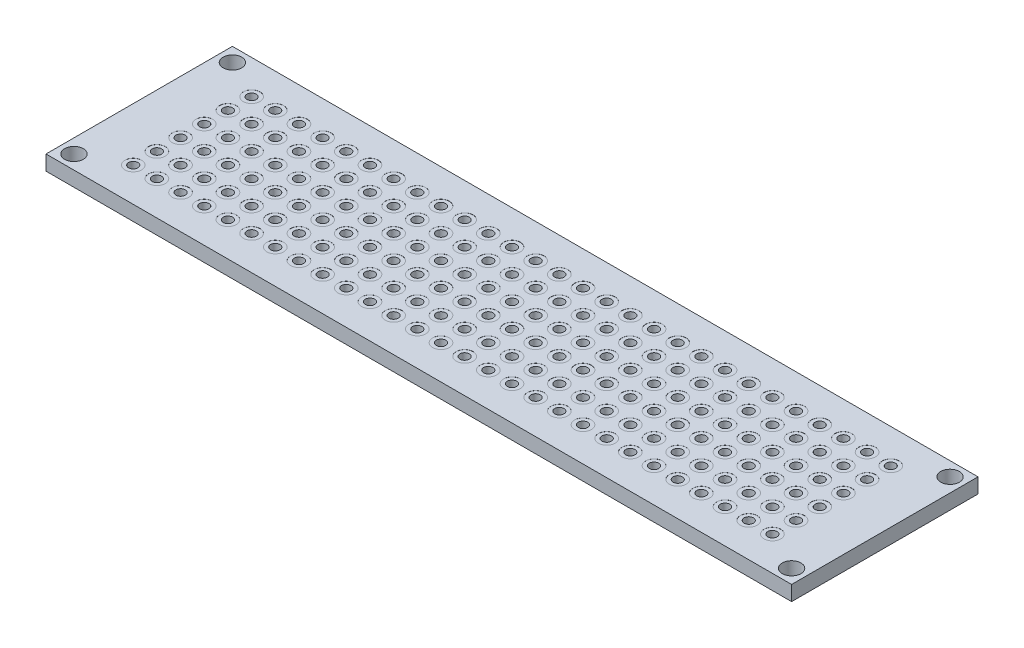
SolidWorks part; units mm, degrees
ref_plane "Front Plane" through (0, 0, 0) normal (0, 0, 1) x (1, 0, 0)
ref_plane "Top Plane" through (0, 0, 0) normal (0, 1, 0) x (1, 0, 0)
ref_plane "Right Plane" through (0, 0, 0) normal (1, 0, 0) x (0, 0, -1)
sketch "Sketch1" plane through (0, 0, 0) normal (0, 1, 0) x (1, 0, 0)
  line L0 (40, 0) -> (40, 20) construction
  line L1 (0, 0) -> (80, 0)
  line L2 (0, 0) -> (0, 20)
  line L3 (0, 20) -> (80, 20)
  line L4 (80, 0) -> (80, 20)
  line L5 (0, 10) -> (80, 10) construction
  circle A0 centre (5.71, 16.35) radius 0.5
  circle A1 centre (5.71, 13.81) radius 0.5
  circle A2 centre (5.71, 11.27) radius 0.5
  circle A3 centre (5.71, 8.73) radius 0.5
  circle A4 centre (5.71, 6.19) radius 0.5
  circle A5 centre (5.71, 3.65) radius 0.5
  circle A6 centre (8.25, 16.35) radius 0.5
  circle A7 centre (8.25, 13.81) radius 0.5
  circle A8 centre (8.25, 11.27) radius 0.5
  circle A9 centre (8.25, 8.73) radius 0.5
  circle A10 centre (8.25, 6.19) radius 0.5
  circle A11 centre (8.25, 3.65) radius 0.5
  circle A12 centre (10.79, 16.35) radius 0.5
  circle A13 centre (10.79, 13.81) radius 0.5
  circle A14 centre (10.79, 11.27) radius 0.5
  circle A15 centre (10.79, 8.73) radius 0.5
  circle A16 centre (10.79, 6.19) radius 0.5
  circle A17 centre (10.79, 3.65) radius 0.5
  circle A18 centre (13.33, 16.35) radius 0.5
  circle A19 centre (13.33, 13.81) radius 0.5
  circle A20 centre (13.33, 11.27) radius 0.5
  circle A21 centre (13.33, 8.73) radius 0.5
  circle A22 centre (13.33, 6.19) radius 0.5
  circle A23 centre (13.33, 3.65) radius 0.5
  circle A24 centre (15.87, 16.35) radius 0.5
  circle A25 centre (15.87, 13.81) radius 0.5
  circle A26 centre (15.87, 11.27) radius 0.5
  circle A27 centre (15.87, 8.73) radius 0.5
  circle A28 centre (15.87, 6.19) radius 0.5
  circle A29 centre (15.87, 3.65) radius 0.5
  circle A30 centre (18.41, 16.35) radius 0.5
  circle A31 centre (18.41, 13.81) radius 0.5
  circle A32 centre (18.41, 11.27) radius 0.5
  circle A33 centre (18.41, 8.73) radius 0.5
  circle A34 centre (18.41, 6.19) radius 0.5
  circle A35 centre (18.41, 3.65) radius 0.5
  circle A36 centre (20.95, 16.35) radius 0.5
  circle A37 centre (20.95, 13.81) radius 0.5
  circle A38 centre (20.95, 11.27) radius 0.5
  circle A39 centre (20.95, 8.73) radius 0.5
  circle A40 centre (20.95, 6.19) radius 0.5
  circle A41 centre (20.95, 3.65) radius 0.5
  circle A42 centre (23.49, 16.35) radius 0.5
  circle A43 centre (23.49, 13.81) radius 0.5
  circle A44 centre (23.49, 11.27) radius 0.5
  circle A45 centre (23.49, 8.73) radius 0.5
  circle A46 centre (23.49, 6.19) radius 0.5
  circle A47 centre (23.49, 3.65) radius 0.5
  circle A48 centre (26.03, 16.35) radius 0.5
  circle A49 centre (26.03, 13.81) radius 0.5
  circle A50 centre (26.03, 11.27) radius 0.5
  circle A51 centre (26.03, 8.73) radius 0.5
  circle A52 centre (26.03, 6.19) radius 0.5
  circle A53 centre (26.03, 3.65) radius 0.5
  circle A54 centre (28.57, 16.35) radius 0.5
  circle A55 centre (28.57, 13.81) radius 0.5
  circle A56 centre (28.57, 11.27) radius 0.5
  circle A57 centre (28.57, 8.73) radius 0.5
  circle A58 centre (28.57, 6.19) radius 0.5
  circle A59 centre (28.57, 3.65) radius 0.5
  circle A60 centre (31.11, 16.35) radius 0.5
  circle A61 centre (31.11, 13.81) radius 0.5
  circle A62 centre (31.11, 11.27) radius 0.5
  circle A63 centre (31.11, 8.73) radius 0.5
  circle A64 centre (31.11, 6.19) radius 0.5
  circle A65 centre (31.11, 3.65) radius 0.5
  circle A66 centre (33.65, 16.35) radius 0.5
  circle A67 centre (33.65, 13.81) radius 0.5
  circle A68 centre (33.65, 11.27) radius 0.5
  circle A69 centre (33.65, 8.73) radius 0.5
  circle A70 centre (33.65, 6.19) radius 0.5
  circle A71 centre (33.65, 3.65) radius 0.5
  circle A72 centre (36.19, 16.35) radius 0.5
  circle A73 centre (36.19, 13.81) radius 0.5
  circle A74 centre (36.19, 11.27) radius 0.5
  circle A75 centre (36.19, 8.73) radius 0.5
  circle A76 centre (36.19, 6.19) radius 0.5
  circle A77 centre (36.19, 3.65) radius 0.5
  circle A78 centre (38.73, 16.35) radius 0.5
  circle A79 centre (38.73, 13.81) radius 0.5
  circle A80 centre (38.73, 11.27) radius 0.5
  circle A81 centre (38.73, 8.73) radius 0.5
  circle A82 centre (38.73, 6.19) radius 0.5
  circle A83 centre (38.73, 3.65) radius 0.5
  circle A84 centre (41.27, 16.35) radius 0.5
  circle A85 centre (41.27, 13.81) radius 0.5
  circle A86 centre (41.27, 11.27) radius 0.5
  circle A87 centre (41.27, 8.73) radius 0.5
  circle A88 centre (41.27, 6.19) radius 0.5
  circle A89 centre (41.27, 3.65) radius 0.5
  circle A90 centre (43.81, 16.35) radius 0.5
  circle A91 centre (43.81, 13.81) radius 0.5
  circle A92 centre (43.81, 11.27) radius 0.5
  circle A93 centre (43.81, 8.73) radius 0.5
  circle A94 centre (43.81, 6.19) radius 0.5
  circle A95 centre (43.81, 3.65) radius 0.5
  circle A96 centre (46.35, 16.35) radius 0.5
  circle A97 centre (46.35, 13.81) radius 0.5
  circle A98 centre (46.35, 11.27) radius 0.5
  circle A99 centre (46.35, 8.73) radius 0.5
  circle A100 centre (46.35, 6.19) radius 0.5
  circle A101 centre (46.35, 3.65) radius 0.5
  circle A102 centre (48.89, 16.35) radius 0.5
  circle A103 centre (48.89, 13.81) radius 0.5
  circle A104 centre (48.89, 11.27) radius 0.5
  circle A105 centre (48.89, 8.73) radius 0.5
  circle A106 centre (48.89, 6.19) radius 0.5
  circle A107 centre (48.89, 3.65) radius 0.5
  circle A108 centre (51.43, 16.35) radius 0.5
  circle A109 centre (51.43, 13.81) radius 0.5
  circle A110 centre (51.43, 11.27) radius 0.5
  circle A111 centre (51.43, 8.73) radius 0.5
  circle A112 centre (51.43, 6.19) radius 0.5
  circle A113 centre (51.43, 3.65) radius 0.5
  circle A114 centre (53.97, 16.35) radius 0.5
  circle A115 centre (53.97, 13.81) radius 0.5
  circle A116 centre (53.97, 11.27) radius 0.5
  circle A117 centre (53.97, 8.73) radius 0.5
  circle A118 centre (53.97, 6.19) radius 0.5
  circle A119 centre (53.97, 3.65) radius 0.5
  circle A120 centre (56.51, 16.35) radius 0.5
  circle A121 centre (56.51, 13.81) radius 0.5
  circle A122 centre (56.51, 11.27) radius 0.5
  circle A123 centre (56.51, 8.73) radius 0.5
  circle A124 centre (56.51, 6.19) radius 0.5
  circle A125 centre (56.51, 3.65) radius 0.5
  circle A126 centre (59.05, 16.35) radius 0.5
  circle A127 centre (59.05, 13.81) radius 0.5
  circle A128 centre (59.05, 11.27) radius 0.5
  circle A129 centre (59.05, 8.73) radius 0.5
  circle A130 centre (59.05, 6.19) radius 0.5
  circle A131 centre (59.05, 3.65) radius 0.5
  circle A132 centre (61.59, 16.35) radius 0.5
  circle A133 centre (61.59, 13.81) radius 0.5
  circle A134 centre (61.59, 11.27) radius 0.5
  circle A135 centre (61.59, 8.73) radius 0.5
  circle A136 centre (61.59, 6.19) radius 0.5
  circle A137 centre (61.59, 3.65) radius 0.5
  circle A138 centre (64.13, 16.35) radius 0.5
  circle A139 centre (64.13, 13.81) radius 0.5
  circle A140 centre (64.13, 11.27) radius 0.5
  circle A141 centre (64.13, 8.73) radius 0.5
  circle A142 centre (64.13, 6.19) radius 0.5
  circle A143 centre (64.13, 3.65) radius 0.5
  circle A144 centre (66.67, 16.35) radius 0.5
  circle A145 centre (66.67, 13.81) radius 0.5
  circle A146 centre (66.67, 11.27) radius 0.5
  circle A147 centre (66.67, 8.73) radius 0.5
  circle A148 centre (66.67, 6.19) radius 0.5
  circle A149 centre (66.67, 3.65) radius 0.5
  circle A150 centre (69.21, 16.35) radius 0.5
  circle A151 centre (69.21, 13.81) radius 0.5
  circle A152 centre (69.21, 11.27) radius 0.5
  circle A153 centre (69.21, 8.73) radius 0.5
  circle A154 centre (69.21, 6.19) radius 0.5
  circle A155 centre (69.21, 3.65) radius 0.5
  circle A156 centre (71.75, 16.35) radius 0.5
  circle A157 centre (71.75, 13.81) radius 0.5
  circle A158 centre (71.75, 11.27) radius 0.5
  circle A159 centre (71.75, 8.73) radius 0.5
  circle A160 centre (71.75, 6.19) radius 0.5
  circle A161 centre (71.75, 3.65) radius 0.5
  circle A162 centre (74.29, 16.35) radius 0.5
  circle A163 centre (74.29, 13.81) radius 0.5
  circle A164 centre (74.29, 11.27) radius 0.5
  circle A165 centre (74.29, 8.73) radius 0.5
  circle A166 centre (74.29, 6.19) radius 0.5
  circle A167 centre (74.29, 3.65) radius 0.5
  circle A168 centre (1.5, 18.5) radius 1
  circle A169 centre (78.5, 18.5) radius 1
  circle A170 centre (1.5, 1.5) radius 1
  circle A171 centre (78.5, 1.5) radius 1
  point P11 (1.3527, 18.7563)
  dimension "D3" = 1
  dimension "D8" = 2
  dimension "D9" = 0.5
  dimension "D10" = 0.5
  dimension "D1" = 80
  dimension "D2" = 20
  dimension "D5" = 2.54
  dimension "D7" = 2.54
  dimension "D4" = 6
  dimension "D6" = 28
extrude "Boss-Extrude1" add sketch "Sketch1" along normal blind 1.6
sketch "Sketch2" plane through (0, 1.6, 0) normal (0, 1, 0) x (1, 0, 0)
  circle A0 centre (5.71, 16.35) radius 0.9
  circle A1 centre (8.25, 16.35) radius 0.9
  circle A2 centre (10.79, 16.35) radius 0.9
  circle A3 centre (13.33, 16.35) radius 0.9
  circle A4 centre (15.87, 16.35) radius 0.9
  circle A5 centre (18.41, 16.35) radius 0.9
  circle A6 centre (20.95, 16.35) radius 0.9
  circle A7 centre (23.49, 16.35) radius 0.9
  circle A8 centre (26.03, 16.35) radius 0.9
  circle A9 centre (28.57, 16.35) radius 0.9
  circle A10 centre (31.11, 16.35) radius 0.9
  circle A11 centre (33.65, 16.35) radius 0.9
  circle A12 centre (36.19, 16.35) radius 0.9
  circle A13 centre (38.73, 16.35) radius 0.9
  circle A14 centre (41.27, 16.35) radius 0.9
  circle A15 centre (43.81, 16.35) radius 0.9
  circle A16 centre (46.35, 16.35) radius 0.9
  circle A17 centre (48.89, 16.35) radius 0.9
  circle A18 centre (51.43, 16.35) radius 0.9
  circle A19 centre (53.97, 16.35) radius 0.9
  circle A20 centre (56.51, 16.35) radius 0.9
  circle A21 centre (59.05, 16.35) radius 0.9
  circle A22 centre (61.59, 16.35) radius 0.9
  circle A23 centre (64.13, 16.35) radius 0.9
  circle A24 centre (66.67, 16.35) radius 0.9
  circle A25 centre (69.21, 16.35) radius 0.9
  circle A26 centre (71.75, 16.35) radius 0.9
  circle A27 centre (74.29, 16.35) radius 0.9
  circle A28 centre (8.25, 13.81) radius 0.9
  circle A29 centre (10.79, 13.81) radius 0.9
  circle A30 centre (13.33, 13.81) radius 0.9
  circle A31 centre (15.87, 13.81) radius 0.9
  circle A32 centre (18.41, 13.81) radius 0.9
  circle A33 centre (20.95, 13.81) radius 0.9
  circle A34 centre (23.49, 13.81) radius 0.9
  circle A35 centre (26.03, 13.81) radius 0.9
  circle A36 centre (28.57, 13.81) radius 0.9
  circle A37 centre (31.11, 13.81) radius 0.9
  circle A38 centre (33.65, 13.81) radius 0.9
  circle A39 centre (36.19, 13.81) radius 0.9
  circle A40 centre (38.73, 13.81) radius 0.9
  circle A41 centre (41.27, 13.81) radius 0.9
  circle A42 centre (43.81, 13.81) radius 0.9
  circle A43 centre (46.35, 13.81) radius 0.9
  circle A44 centre (48.89, 13.81) radius 0.9
  circle A45 centre (51.43, 13.81) radius 0.9
  circle A46 centre (53.97, 13.81) radius 0.9
  circle A47 centre (56.51, 13.81) radius 0.9
  circle A48 centre (59.05, 13.81) radius 0.9
  circle A49 centre (61.59, 13.81) radius 0.9
  circle A50 centre (64.13, 13.81) radius 0.9
  circle A51 centre (66.67, 13.81) radius 0.9
  circle A52 centre (69.21, 13.81) radius 0.9
  circle A53 centre (71.75, 13.81) radius 0.9
  circle A54 centre (74.29, 13.81) radius 0.9
  circle A55 centre (8.25, 11.27) radius 0.9
  circle A56 centre (10.79, 11.27) radius 0.9
  circle A57 centre (13.33, 11.27) radius 0.9
  circle A58 centre (15.87, 11.27) radius 0.9
  circle A59 centre (18.41, 11.27) radius 0.9
  circle A60 centre (20.95, 11.27) radius 0.9
  circle A61 centre (23.49, 11.27) radius 0.9
  circle A62 centre (26.03, 11.27) radius 0.9
  circle A63 centre (28.57, 11.27) radius 0.9
  circle A64 centre (31.11, 11.27) radius 0.9
  circle A65 centre (33.65, 11.27) radius 0.9
  circle A66 centre (36.19, 11.27) radius 0.9
  circle A67 centre (38.73, 11.27) radius 0.9
  circle A68 centre (41.27, 11.27) radius 0.9
  circle A69 centre (43.81, 11.27) radius 0.9
  circle A70 centre (46.35, 11.27) radius 0.9
  circle A71 centre (48.89, 11.27) radius 0.9
  circle A72 centre (51.43, 11.27) radius 0.9
  circle A73 centre (53.97, 11.27) radius 0.9
  circle A74 centre (56.51, 11.27) radius 0.9
  circle A75 centre (59.05, 11.27) radius 0.9
  circle A76 centre (61.59, 11.27) radius 0.9
  circle A77 centre (64.13, 11.27) radius 0.9
  circle A78 centre (66.67, 11.27) radius 0.9
  circle A79 centre (69.21, 11.27) radius 0.9
  circle A80 centre (71.75, 11.27) radius 0.9
  circle A81 centre (74.29, 11.27) radius 0.9
  circle A82 centre (8.25, 8.73) radius 0.9
  circle A83 centre (10.79, 8.73) radius 0.9
  circle A84 centre (13.33, 8.73) radius 0.9
  circle A85 centre (15.87, 8.73) radius 0.9
  circle A86 centre (18.41, 8.73) radius 0.9
  circle A87 centre (20.95, 8.73) radius 0.9
  circle A88 centre (23.49, 8.73) radius 0.9
  circle A89 centre (26.03, 8.73) radius 0.9
  circle A90 centre (28.57, 8.73) radius 0.9
  circle A91 centre (31.11, 8.73) radius 0.9
  circle A92 centre (33.65, 8.73) radius 0.9
  circle A93 centre (36.19, 8.73) radius 0.9
  circle A94 centre (38.73, 8.73) radius 0.9
  circle A95 centre (41.27, 8.73) radius 0.9
  circle A96 centre (43.81, 8.73) radius 0.9
  circle A97 centre (46.35, 8.73) radius 0.9
  circle A98 centre (48.89, 8.73) radius 0.9
  circle A99 centre (51.43, 8.73) radius 0.9
  circle A100 centre (53.97, 8.73) radius 0.9
  circle A101 centre (56.51, 8.73) radius 0.9
  circle A102 centre (59.05, 8.73) radius 0.9
  circle A103 centre (61.59, 8.73) radius 0.9
  circle A104 centre (64.13, 8.73) radius 0.9
  circle A105 centre (66.67, 8.73) radius 0.9
  circle A106 centre (69.21, 8.73) radius 0.9
  circle A107 centre (71.75, 8.73) radius 0.9
  circle A108 centre (74.29, 8.73) radius 0.9
  circle A109 centre (8.25, 6.19) radius 0.9
  circle A110 centre (10.79, 6.19) radius 0.9
  circle A111 centre (13.33, 6.19) radius 0.9
  circle A112 centre (15.87, 6.19) radius 0.9
  circle A113 centre (18.41, 6.19) radius 0.9
  circle A114 centre (20.95, 6.19) radius 0.9
  circle A115 centre (23.49, 6.19) radius 0.9
  circle A116 centre (26.03, 6.19) radius 0.9
  circle A117 centre (28.57, 6.19) radius 0.9
  circle A118 centre (31.11, 6.19) radius 0.9
  circle A119 centre (33.65, 6.19) radius 0.9
  circle A120 centre (36.19, 6.19) radius 0.9
  circle A121 centre (38.73, 6.19) radius 0.9
  circle A122 centre (41.27, 6.19) radius 0.9
  circle A123 centre (43.81, 6.19) radius 0.9
  circle A124 centre (46.35, 6.19) radius 0.9
  circle A125 centre (48.89, 6.19) radius 0.9
  circle A126 centre (51.43, 6.19) radius 0.9
  circle A127 centre (53.97, 6.19) radius 0.9
  circle A128 centre (56.51, 6.19) radius 0.9
  circle A129 centre (59.05, 6.19) radius 0.9
  circle A130 centre (61.59, 6.19) radius 0.9
  circle A131 centre (64.13, 6.19) radius 0.9
  circle A132 centre (66.67, 6.19) radius 0.9
  circle A133 centre (69.21, 6.19) radius 0.9
  circle A134 centre (71.75, 6.19) radius 0.9
  circle A135 centre (74.29, 6.19) radius 0.9
  circle A136 centre (8.25, 3.65) radius 0.9
  circle A137 centre (10.79, 3.65) radius 0.9
  circle A138 centre (13.33, 3.65) radius 0.9
  circle A139 centre (15.87, 3.65) radius 0.9
  circle A140 centre (18.41, 3.65) radius 0.9
  circle A141 centre (20.95, 3.65) radius 0.9
  circle A142 centre (23.49, 3.65) radius 0.9
  circle A143 centre (26.03, 3.65) radius 0.9
  circle A144 centre (28.57, 3.65) radius 0.9
  circle A145 centre (31.11, 3.65) radius 0.9
  circle A146 centre (33.65, 3.65) radius 0.9
  circle A147 centre (36.19, 3.65) radius 0.9
  circle A148 centre (38.73, 3.65) radius 0.9
  circle A149 centre (41.27, 3.65) radius 0.9
  circle A150 centre (43.81, 3.65) radius 0.9
  circle A151 centre (46.35, 3.65) radius 0.9
  circle A152 centre (48.89, 3.65) radius 0.9
  circle A153 centre (51.43, 3.65) radius 0.9
  circle A154 centre (53.97, 3.65) radius 0.9
  circle A155 centre (56.51, 3.65) radius 0.9
  circle A156 centre (59.05, 3.65) radius 0.9
  circle A157 centre (61.59, 3.65) radius 0.9
  circle A158 centre (64.13, 3.65) radius 0.9
  circle A159 centre (66.67, 3.65) radius 0.9
  circle A160 centre (69.21, 3.65) radius 0.9
  circle A161 centre (71.75, 3.65) radius 0.9
  circle A162 centre (74.29, 3.65) radius 0.9
  circle A163 centre (5.71, 13.81) radius 0.9
  circle A164 centre (5.71, 11.27) radius 0.9
  circle A165 centre (5.71, 8.73) radius 0.9
  circle A166 centre (5.71, 6.19) radius 0.9
  circle A167 centre (5.71, 3.65) radius 0.9
  point P4 (5.71, 13.81)
  point P5 (8.25, 16.35)
  dimension "D1" = 1.8
  dimension "D2" = 28
  dimension "D3" = 6
extrude "Cut-Extrude1" cut sketch "Sketch2" against normal blind 0.01
sketch "Sketch3" plane through (0, 0, 0) normal (0, -1, 0) x (1, 0, 0)
  circle A1 centre (20.95, -3.65) radius 0.9
  circle A2 centre (20.95, -3.65) radius 0.9
  circle A3 centre (18.41, -3.65) radius 0.9
  circle A4 centre (18.41, -3.65) radius 0.9
  circle A5 centre (15.87, -3.65) radius 0.9
  circle A6 centre (15.87, -3.65) radius 0.9
  circle A7 centre (13.33, -3.65) radius 0.9
  circle A8 centre (13.33, -3.65) radius 0.9
  circle A9 centre (10.79, -3.65) radius 0.9
  circle A10 centre (10.79, -3.65) radius 0.9
  circle A11 centre (8.25, -3.65) radius 0.9
  circle A12 centre (8.25, -3.65) radius 0.9
  circle A13 centre (74.29, -6.19) radius 0.9
  circle A14 centre (74.29, -6.19) radius 0.9
  circle A15 centre (71.75, -6.19) radius 0.9
  circle A16 centre (71.75, -6.19) radius 0.9
  circle A17 centre (18.41, -16.35) radius 0.9
  circle A18 centre (18.41, -16.35) radius 0.9
  circle A19 centre (15.87, -16.35) radius 0.9
  circle A20 centre (15.87, -16.35) radius 0.9
  circle A21 centre (13.33, -16.35) radius 0.9
  circle A22 centre (13.33, -16.35) radius 0.9
  circle A23 centre (10.79, -16.35) radius 0.9
  circle A24 centre (10.79, -16.35) radius 0.9
  circle A25 centre (8.25, -16.35) radius 0.9
  circle A26 centre (8.25, -16.35) radius 0.9
  circle A27 centre (5.71, -16.35) radius 0.9
  circle A28 centre (5.71, -16.35) radius 0.9
  circle A29 centre (41.27, -3.65) radius 0.9
  circle A30 centre (41.27, -3.65) radius 0.9
  circle A31 centre (38.73, -3.65) radius 0.9
  circle A32 centre (38.73, -3.65) radius 0.9
  circle A33 centre (36.19, -3.65) radius 0.9
  circle A34 centre (36.19, -3.65) radius 0.9
  circle A35 centre (33.65, -3.65) radius 0.9
  circle A36 centre (33.65, -3.65) radius 0.9
  circle A37 centre (31.11, -3.65) radius 0.9
  circle A38 centre (31.11, -3.65) radius 0.9
  circle A39 centre (28.57, -3.65) radius 0.9
  circle A40 centre (28.57, -3.65) radius 0.9
  circle A41 centre (26.03, -3.65) radius 0.9
  circle A42 centre (26.03, -3.65) radius 0.9
  circle A43 centre (23.49, -3.65) radius 0.9
  circle A44 centre (23.49, -3.65) radius 0.9
  circle A45 centre (38.73, -16.35) radius 0.9
  circle A46 centre (38.73, -16.35) radius 0.9
  circle A47 centre (36.19, -16.35) radius 0.9
  circle A48 centre (36.19, -16.35) radius 0.9
  circle A49 centre (33.65, -16.35) radius 0.9
  circle A50 centre (33.65, -16.35) radius 0.9
  circle A51 centre (31.11, -16.35) radius 0.9
  circle A52 centre (31.11, -16.35) radius 0.9
  circle A53 centre (28.57, -16.35) radius 0.9
  circle A54 centre (28.57, -16.35) radius 0.9
  circle A55 centre (26.03, -16.35) radius 0.9
  circle A56 centre (26.03, -16.35) radius 0.9
  circle A57 centre (23.49, -16.35) radius 0.9
  circle A58 centre (23.49, -16.35) radius 0.9
  circle A59 centre (20.95, -16.35) radius 0.9
  circle A60 centre (20.95, -16.35) radius 0.9
  circle A61 centre (61.59, -3.65) radius 0.9
  circle A62 centre (61.59, -3.65) radius 0.9
  circle A63 centre (59.05, -3.65) radius 0.9
  circle A64 centre (59.05, -3.65) radius 0.9
  circle A65 centre (56.51, -3.65) radius 0.9
  circle A66 centre (56.51, -3.65) radius 0.9
  circle A67 centre (53.97, -3.65) radius 0.9
  circle A68 centre (53.97, -3.65) radius 0.9
  circle A69 centre (51.43, -3.65) radius 0.9
  circle A70 centre (51.43, -3.65) radius 0.9
  circle A71 centre (48.89, -3.65) radius 0.9
  circle A72 centre (48.89, -3.65) radius 0.9
  circle A73 centre (46.35, -3.65) radius 0.9
  circle A74 centre (46.35, -3.65) radius 0.9
  circle A75 centre (43.81, -3.65) radius 0.9
  circle A76 centre (43.81, -3.65) radius 0.9
  circle A77 centre (59.05, -16.35) radius 0.9
  circle A78 centre (59.05, -16.35) radius 0.9
  circle A79 centre (56.51, -16.35) radius 0.9
  circle A80 centre (56.51, -16.35) radius 0.9
  circle A81 centre (53.97, -16.35) radius 0.9
  circle A82 centre (53.97, -16.35) radius 0.9
  circle A83 centre (51.43, -16.35) radius 0.9
  circle A84 centre (51.43, -16.35) radius 0.9
  circle A85 centre (48.89, -16.35) radius 0.9
  circle A86 centre (48.89, -16.35) radius 0.9
  circle A87 centre (46.35, -16.35) radius 0.9
  circle A88 centre (46.35, -16.35) radius 0.9
  circle A89 centre (43.81, -16.35) radius 0.9
  circle A90 centre (43.81, -16.35) radius 0.9
  circle A91 centre (41.27, -16.35) radius 0.9
  circle A92 centre (41.27, -16.35) radius 0.9
  circle A93 centre (5.71, -8.73) radius 0.9
  circle A94 centre (5.71, -8.73) radius 0.9
  circle A95 centre (5.71, -11.27) radius 0.9
  circle A96 centre (5.71, -11.27) radius 0.9
  circle A97 centre (5.71, -13.81) radius 0.9
  circle A98 centre (5.71, -13.81) radius 0.9
  circle A99 centre (74.29, -3.65) radius 0.9
  circle A100 centre (74.29, -3.65) radius 0.9
  circle A101 centre (71.75, -3.65) radius 0.9
  circle A102 centre (71.75, -3.65) radius 0.9
  circle A103 centre (69.21, -3.65) radius 0.9
  circle A104 centre (69.21, -3.65) radius 0.9
  circle A105 centre (66.67, -3.65) radius 0.9
  circle A106 centre (66.67, -3.65) radius 0.9
  circle A107 centre (64.13, -3.65) radius 0.9
  circle A108 centre (64.13, -3.65) radius 0.9
  circle A109 centre (10.79, -13.81) radius 0.9
  circle A110 centre (10.79, -13.81) radius 0.9
  circle A111 centre (8.25, -13.81) radius 0.9
  circle A112 centre (8.25, -13.81) radius 0.9
  circle A113 centre (74.29, -16.35) radius 0.9
  circle A114 centre (74.29, -16.35) radius 0.9
  circle A115 centre (71.75, -16.35) radius 0.9
  circle A116 centre (71.75, -16.35) radius 0.9
  circle A117 centre (69.21, -16.35) radius 0.9
  circle A118 centre (69.21, -16.35) radius 0.9
  circle A119 centre (66.67, -16.35) radius 0.9
  circle A120 centre (66.67, -16.35) radius 0.9
  circle A121 centre (64.13, -16.35) radius 0.9
  circle A122 centre (64.13, -16.35) radius 0.9
  circle A123 centre (61.59, -16.35) radius 0.9
  circle A124 centre (61.59, -16.35) radius 0.9
  circle A125 centre (5.71, -3.65) radius 0.9
  circle A126 centre (5.71, -3.65) radius 0.9
  circle A127 centre (5.71, -6.19) radius 0.9
  circle A128 centre (5.71, -6.19) radius 0.9
  circle A129 centre (31.11, -13.81) radius 0.9
  circle A130 centre (31.11, -13.81) radius 0.9
  circle A131 centre (28.57, -13.81) radius 0.9
  circle A132 centre (28.57, -13.81) radius 0.9
  circle A133 centre (26.03, -13.81) radius 0.9
  circle A134 centre (26.03, -13.81) radius 0.9
  circle A135 centre (23.49, -13.81) radius 0.9
  circle A136 centre (23.49, -13.81) radius 0.9
  circle A137 centre (20.95, -13.81) radius 0.9
  circle A138 centre (20.95, -13.81) radius 0.9
  circle A139 centre (18.41, -13.81) radius 0.9
  circle A140 centre (18.41, -13.81) radius 0.9
  circle A141 centre (15.87, -13.81) radius 0.9
  circle A142 centre (15.87, -13.81) radius 0.9
  circle A143 centre (13.33, -13.81) radius 0.9
  circle A144 centre (13.33, -13.81) radius 0.9
  circle A145 centre (51.43, -13.81) radius 0.9
  circle A146 centre (51.43, -13.81) radius 0.9
  circle A147 centre (48.89, -13.81) radius 0.9
  circle A148 centre (48.89, -13.81) radius 0.9
  circle A149 centre (46.35, -13.81) radius 0.9
  circle A150 centre (46.35, -13.81) radius 0.9
  circle A151 centre (43.81, -13.81) radius 0.9
  circle A152 centre (43.81, -13.81) radius 0.9
  circle A153 centre (41.27, -13.81) radius 0.9
  circle A154 centre (41.27, -13.81) radius 0.9
  circle A155 centre (38.73, -13.81) radius 0.9
  circle A156 centre (38.73, -13.81) radius 0.9
  circle A157 centre (36.19, -13.81) radius 0.9
  circle A158 centre (36.19, -13.81) radius 0.9
  circle A159 centre (33.65, -13.81) radius 0.9
  circle A160 centre (33.65, -13.81) radius 0.9
  circle A161 centre (71.75, -13.81) radius 0.9
  circle A162 centre (71.75, -13.81) radius 0.9
  circle A163 centre (69.21, -13.81) radius 0.9
  circle A164 centre (69.21, -13.81) radius 0.9
  circle A165 centre (66.67, -13.81) radius 0.9
  circle A166 centre (66.67, -13.81) radius 0.9
  circle A167 centre (64.13, -13.81) radius 0.9
  circle A168 centre (64.13, -13.81) radius 0.9
  circle A169 centre (61.59, -13.81) radius 0.9
  circle A170 centre (61.59, -13.81) radius 0.9
  circle A171 centre (59.05, -13.81) radius 0.9
  circle A172 centre (59.05, -13.81) radius 0.9
  circle A173 centre (56.51, -13.81) radius 0.9
  circle A174 centre (56.51, -13.81) radius 0.9
  circle A175 centre (53.97, -13.81) radius 0.9
  circle A176 centre (53.97, -13.81) radius 0.9
  circle A177 centre (23.49, -11.27) radius 0.9
  circle A178 centre (23.49, -11.27) radius 0.9
  circle A179 centre (20.95, -11.27) radius 0.9
  circle A180 centre (20.95, -11.27) radius 0.9
  circle A181 centre (18.41, -11.27) radius 0.9
  circle A182 centre (18.41, -11.27) radius 0.9
  circle A183 centre (15.87, -11.27) radius 0.9
  circle A184 centre (15.87, -11.27) radius 0.9
  circle A185 centre (13.33, -11.27) radius 0.9
  circle A186 centre (13.33, -11.27) radius 0.9
  circle A187 centre (10.79, -11.27) radius 0.9
  circle A188 centre (10.79, -11.27) radius 0.9
  circle A189 centre (8.25, -11.27) radius 0.9
  circle A190 centre (8.25, -11.27) radius 0.9
  circle A191 centre (74.29, -13.81) radius 0.9
  circle A192 centre (74.29, -13.81) radius 0.9
  circle A193 centre (43.81, -11.27) radius 0.9
  circle A194 centre (43.81, -11.27) radius 0.9
  circle A195 centre (41.27, -11.27) radius 0.9
  circle A196 centre (41.27, -11.27) radius 0.9
  circle A197 centre (38.73, -11.27) radius 0.9
  circle A198 centre (38.73, -11.27) radius 0.9
  circle A199 centre (36.19, -11.27) radius 0.9
  circle A200 centre (36.19, -11.27) radius 0.9
  circle A201 centre (33.65, -11.27) radius 0.9
  circle A202 centre (33.65, -11.27) radius 0.9
  circle A203 centre (31.11, -11.27) radius 0.9
  circle A204 centre (31.11, -11.27) radius 0.9
  circle A205 centre (28.57, -11.27) radius 0.9
  circle A206 centre (28.57, -11.27) radius 0.9
  circle A207 centre (26.03, -11.27) radius 0.9
  circle A208 centre (26.03, -11.27) radius 0.9
  circle A209 centre (64.13, -11.27) radius 0.9
  circle A210 centre (64.13, -11.27) radius 0.9
  circle A211 centre (61.59, -11.27) radius 0.9
  circle A212 centre (61.59, -11.27) radius 0.9
  circle A213 centre (59.05, -11.27) radius 0.9
  circle A214 centre (59.05, -11.27) radius 0.9
  circle A215 centre (56.51, -11.27) radius 0.9
  circle A216 centre (56.51, -11.27) radius 0.9
  circle A217 centre (53.97, -11.27) radius 0.9
  circle A218 centre (53.97, -11.27) radius 0.9
  circle A219 centre (51.43, -11.27) radius 0.9
  circle A220 centre (51.43, -11.27) radius 0.9
  circle A221 centre (48.89, -11.27) radius 0.9
  circle A222 centre (48.89, -11.27) radius 0.9
  circle A223 centre (46.35, -11.27) radius 0.9
  circle A224 centre (46.35, -11.27) radius 0.9
  circle A225 centre (15.87, -8.73) radius 0.9
  circle A226 centre (15.87, -8.73) radius 0.9
  circle A227 centre (13.33, -8.73) radius 0.9
  circle A228 centre (13.33, -8.73) radius 0.9
  circle A229 centre (10.79, -8.73) radius 0.9
  circle A230 centre (10.79, -8.73) radius 0.9
  circle A231 centre (8.25, -8.73) radius 0.9
  circle A232 centre (8.25, -8.73) radius 0.9
  circle A233 centre (74.29, -11.27) radius 0.9
  circle A234 centre (74.29, -11.27) radius 0.9
  circle A235 centre (71.75, -11.27) radius 0.9
  circle A236 centre (71.75, -11.27) radius 0.9
  circle A237 centre (69.21, -11.27) radius 0.9
  circle A238 centre (69.21, -11.27) radius 0.9
  circle A239 centre (66.67, -11.27) radius 0.9
  circle A240 centre (66.67, -11.27) radius 0.9
  circle A241 centre (36.19, -8.73) radius 0.9
  circle A242 centre (36.19, -8.73) radius 0.9
  circle A243 centre (33.65, -8.73) radius 0.9
  circle A244 centre (33.65, -8.73) radius 0.9
  circle A245 centre (31.11, -8.73) radius 0.9
  circle A246 centre (31.11, -8.73) radius 0.9
  circle A247 centre (28.57, -8.73) radius 0.9
  circle A248 centre (28.57, -8.73) radius 0.9
  circle A249 centre (26.03, -8.73) radius 0.9
  circle A250 centre (26.03, -8.73) radius 0.9
  circle A251 centre (23.49, -8.73) radius 0.9
  circle A252 centre (23.49, -8.73) radius 0.9
  circle A253 centre (20.95, -8.73) radius 0.9
  circle A254 centre (20.95, -8.73) radius 0.9
  circle A255 centre (18.41, -8.73) radius 0.9
  circle A256 centre (18.41, -8.73) radius 0.9
  circle A257 centre (56.51, -8.73) radius 0.9
  circle A258 centre (56.51, -8.73) radius 0.9
  circle A259 centre (53.97, -8.73) radius 0.9
  circle A260 centre (53.97, -8.73) radius 0.9
  circle A261 centre (51.43, -8.73) radius 0.9
  circle A262 centre (51.43, -8.73) radius 0.9
  circle A263 centre (48.89, -8.73) radius 0.9
  circle A264 centre (48.89, -8.73) radius 0.9
  circle A265 centre (46.35, -8.73) radius 0.9
  circle A266 centre (46.35, -8.73) radius 0.9
  circle A267 centre (43.81, -8.73) radius 0.9
  circle A268 centre (43.81, -8.73) radius 0.9
  circle A269 centre (41.27, -8.73) radius 0.9
  circle A270 centre (41.27, -8.73) radius 0.9
  circle A271 centre (38.73, -8.73) radius 0.9
  circle A272 centre (38.73, -8.73) radius 0.9
  circle A273 centre (8.25, -6.19) radius 0.9
  circle A274 centre (8.25, -6.19) radius 0.9
  circle A275 centre (74.29, -8.73) radius 0.9
  circle A276 centre (74.29, -8.73) radius 0.9
  circle A277 centre (71.75, -8.73) radius 0.9
  circle A278 centre (71.75, -8.73) radius 0.9
  circle A279 centre (69.21, -8.73) radius 0.9
  circle A280 centre (69.21, -8.73) radius 0.9
  circle A281 centre (66.67, -8.73) radius 0.9
  circle A282 centre (66.67, -8.73) radius 0.9
  circle A283 centre (64.13, -8.73) radius 0.9
  circle A284 centre (64.13, -8.73) radius 0.9
  circle A285 centre (61.59, -8.73) radius 0.9
  circle A286 centre (61.59, -8.73) radius 0.9
  circle A287 centre (59.05, -8.73) radius 0.9
  circle A288 centre (59.05, -8.73) radius 0.9
  circle A289 centre (28.57, -6.19) radius 0.9
  circle A290 centre (28.57, -6.19) radius 0.9
  circle A291 centre (26.03, -6.19) radius 0.9
  circle A292 centre (26.03, -6.19) radius 0.9
  circle A293 centre (23.49, -6.19) radius 0.9
  circle A294 centre (23.49, -6.19) radius 0.9
  circle A295 centre (20.95, -6.19) radius 0.9
  circle A296 centre (20.95, -6.19) radius 0.9
  circle A297 centre (18.41, -6.19) radius 0.9
  circle A298 centre (18.41, -6.19) radius 0.9
  circle A299 centre (15.87, -6.19) radius 0.9
  circle A300 centre (15.87, -6.19) radius 0.9
  circle A301 centre (13.33, -6.19) radius 0.9
  circle A302 centre (13.33, -6.19) radius 0.9
  circle A303 centre (10.79, -6.19) radius 0.9
  circle A304 centre (10.79, -6.19) radius 0.9
  circle A305 centre (48.89, -6.19) radius 0.9
  circle A306 centre (48.89, -6.19) radius 0.9
  circle A307 centre (46.35, -6.19) radius 0.9
  circle A308 centre (46.35, -6.19) radius 0.9
  circle A309 centre (43.81, -6.19) radius 0.9
  circle A310 centre (43.81, -6.19) radius 0.9
  circle A311 centre (41.27, -6.19) radius 0.9
  circle A312 centre (41.27, -6.19) radius 0.9
  circle A313 centre (38.73, -6.19) radius 0.9
  circle A314 centre (38.73, -6.19) radius 0.9
  circle A315 centre (36.19, -6.19) radius 0.9
  circle A316 centre (36.19, -6.19) radius 0.9
  circle A317 centre (33.65, -6.19) radius 0.9
  circle A318 centre (33.65, -6.19) radius 0.9
  circle A319 centre (31.11, -6.19) radius 0.9
  circle A320 centre (31.11, -6.19) radius 0.9
  circle A321 centre (69.21, -6.19) radius 0.9
  circle A322 centre (69.21, -6.19) radius 0.9
  circle A323 centre (66.67, -6.19) radius 0.9
  circle A324 centre (66.67, -6.19) radius 0.9
  circle A325 centre (64.13, -6.19) radius 0.9
  circle A326 centre (64.13, -6.19) radius 0.9
  circle A327 centre (61.59, -6.19) radius 0.9
  circle A328 centre (61.59, -6.19) radius 0.9
  circle A329 centre (59.05, -6.19) radius 0.9
  circle A330 centre (59.05, -6.19) radius 0.9
  circle A331 centre (56.51, -6.19) radius 0.9
  circle A332 centre (56.51, -6.19) radius 0.9
  circle A333 centre (53.97, -6.19) radius 0.9
  circle A334 centre (53.97, -6.19) radius 0.9
  circle A335 centre (51.43, -6.19) radius 0.9
  circle A336 centre (51.43, -6.19) radius 0.9
  dimension "D1" = 0
  dimension "D2" = 0
  dimension "D3" = 0
  dimension "D4" = 0
  dimension "D5" = 0
  dimension "D6" = 0
  dimension "D7" = 0
  dimension "D8" = 0
  dimension "D9" = 0
  dimension "D10" = 0
  dimension "D11" = 0
  dimension "D12" = 0
  dimension "D13" = 0
  dimension "D14" = 0
  dimension "D15" = 0
  dimension "D16" = 0
  dimension "D17" = 0
  dimension "D18" = 0
  dimension "D19" = 0
  dimension "D20" = 0
  dimension "D21" = 0
  dimension "D22" = 0
  dimension "D23" = 0
  dimension "D24" = 0
  dimension "D25" = 0
  dimension "D26" = 0
  dimension "D27" = 0
  dimension "D28" = 0
  dimension "D29" = 0
  dimension "D30" = 0
  dimension "D31" = 0
  dimension "D32" = 0
  dimension "D33" = 0
  dimension "D34" = 0
  dimension "D35" = 0
  dimension "D36" = 0
  dimension "D37" = 0
  dimension "D38" = 0
  dimension "D39" = 0
  dimension "D40" = 0
  dimension "D41" = 0
  dimension "D42" = 0
  dimension "D43" = 0
  dimension "D44" = 0
  dimension "D45" = 0
  dimension "D46" = 0
  dimension "D47" = 0
  dimension "D48" = 0
  dimension "D49" = 0
  dimension "D50" = 0
  dimension "D51" = 0
  dimension "D52" = 0
  dimension "D53" = 0
  dimension "D54" = 0
  dimension "D55" = 0
  dimension "D56" = 0
  dimension "D57" = 0
  dimension "D58" = 0
  dimension "D59" = 0
  dimension "D60" = 0
  dimension "D61" = 0
  dimension "D62" = 0
  dimension "D63" = 0
  dimension "D64" = 0
  dimension "D65" = 0
  dimension "D66" = 0
  dimension "D67" = 0
  dimension "D68" = 0
  dimension "D69" = 0
  dimension "D70" = 0
  dimension "D71" = 0
  dimension "D72" = 0
  dimension "D73" = 0
  dimension "D74" = 0
  dimension "D75" = 0
  dimension "D76" = 0
  dimension "D77" = 0
  dimension "D78" = 0
  dimension "D79" = 0
  dimension "D80" = 0
  dimension "D81" = 0
  dimension "D82" = 0
  dimension "D83" = 0
  dimension "D84" = 0
  dimension "D85" = 0
  dimension "D86" = 0
  dimension "D87" = 0
  dimension "D88" = 0
  dimension "D89" = 0
  dimension "D90" = 0
  dimension "D91" = 0
  dimension "D92" = 0
  dimension "D93" = 0
  dimension "D94" = 0
  dimension "D95" = 0
  dimension "D96" = 0
  dimension "D97" = 0
  dimension "D98" = 0
  dimension "D99" = 0
  dimension "D100" = 0
  dimension "D101" = 0
  dimension "D102" = 0
  dimension "D103" = 0
  dimension "D104" = 0
  dimension "D105" = 0
  dimension "D106" = 0
  dimension "D107" = 0
  dimension "D108" = 0
  dimension "D109" = 0
  dimension "D110" = 0
  dimension "D111" = 0
  dimension "D112" = 0
  dimension "D113" = 0
  dimension "D114" = 0
  dimension "D115" = 0
  dimension "D116" = 0
  dimension "D117" = 0
  dimension "D118" = 0
  dimension "D119" = 0
  dimension "D120" = 0
  dimension "D121" = 0
  dimension "D122" = 0
  dimension "D123" = 0
  dimension "D124" = 0
  dimension "D125" = 0
  dimension "D126" = 0
  dimension "D127" = 0
  dimension "D128" = 0
  dimension "D129" = 0
  dimension "D130" = 0
  dimension "D131" = 0
  dimension "D132" = 0
  dimension "D133" = 0
  dimension "D134" = 0
  dimension "D135" = 0
  dimension "D136" = 0
  dimension "D137" = 0
  dimension "D138" = 0
  dimension "D139" = 0
  dimension "D140" = 0
  dimension "D141" = 0
  dimension "D142" = 0
  dimension "D143" = 0
  dimension "D144" = 0
  dimension "D145" = 0
  dimension "D146" = 0
  dimension "D147" = 0
  dimension "D148" = 0
  dimension "D149" = 0
  dimension "D150" = 0
  dimension "D151" = 0
  dimension "D152" = 0
  dimension "D153" = 0
  dimension "D154" = 0
  dimension "D155" = 0
  dimension "D156" = 0
  dimension "D157" = 0
  dimension "D158" = 0
  dimension "D159" = 0
  dimension "D160" = 0
  dimension "D161" = 0
  dimension "D162" = 0
  dimension "D163" = 0
  dimension "D164" = 0
  dimension "D165" = 0
  dimension "D166" = 0
  dimension "D167" = 0
  dimension "D168" = 0
extrude "Cut-Extrude2" cut sketch "Sketch3" against normal blind 0.01
